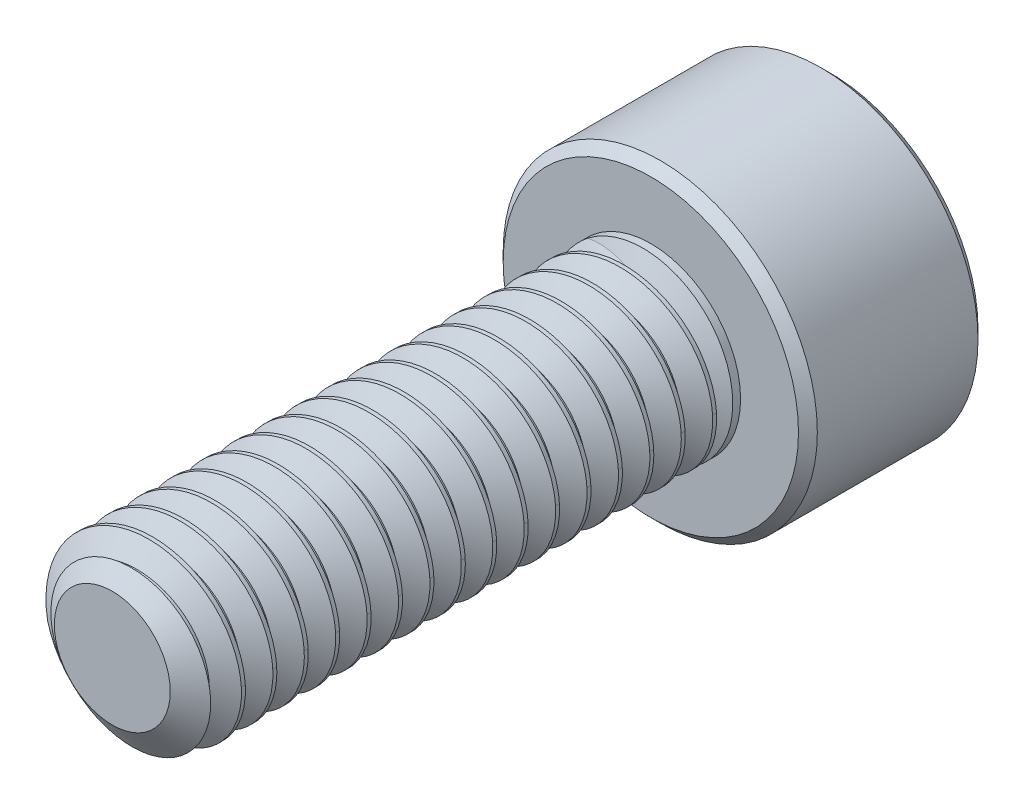
SolidWorks part; units mm, degrees
ref_plane "Front Plane" through (0, 0, 0) normal (0, 0, 1) x (1, 0, 0)
ref_plane "Top Plane" through (0, 0, 0) normal (0, 1, 0) x (1, 0, 0)
ref_plane "Right Plane" through (0, 0, 0) normal (1, 0, 0) x (0, 0, -1)
sketch "Sketch1" plane through (0, 0, 0) normal (0, 0, 1) x (1, 0, 0)
  circle A0 centre (0, 0) radius 2
  dimension "OD" = 4
extrude "Extrude1" add sketch "Sketch1" against normal blind 12
sketch "Sketch2" plane through (0, 0, 0) normal (0, 0, 1) x (1, 0, 0)
  circle A0 centre (0, 0) radius 2 construction
  circle A1 centre (0, 0) radius 2
curve "Helix/Spiral1" pitch 0.7 height 12.7 radius 2 centre (0, 0, 0) axis (0, 0, -1) start towards (0, 1, 0) parameters "pitch"=0.7
sketch "Sketch3" plane through (0, 0, 0) normal (1, 0, 0) x (0, 0, -1)
  line L0 (-0.6125, 2) -> (-0.35, 1.5453)
  line L1 (-0.35, 1.5453) -> (-0.2625, 1.5453)
  line L2 (-0.2625, 1.5453) -> (0, 2)
  line L3 (-0.6125, 2) -> (0, 2)
  line L4 (-0.3063, 2) -> (-0.3063, 1.5453) construction
  line L5 (-0.4813, 1.7727) -> (-0.1313, 1.7727) construction
  line L6 (0, 2) -> (0, -2) construction
  line L7 (0, -2) -> (12, -2) construction
  point P11 (3.15, -2)
  dimension "D1" = 0.0875
  dimension "D2" = 0.35
  dimension "D3" = 60
  dimension "D4" = 3.15
sweep "Cut-Sweep1" cut profiles "Sketch3" path "Helix/Spiral1" align with end faces yes
sketch "Sketch4" plane through (0, 0, 0) normal (1, 0, 0) x (0, 0, -1)
  line L0 (0.4962, 2) -> (0, 1.2913)
  line L1 (0, 1.2913) -> (0, 2)
  line L2 (0.4962, 2) -> (0, 2)
  line L3 (-0.6125, 2) -> (0, 2) construction
  line L4 (0, 0) -> (7.0209, 0) construction
  dimension "D1" = 55
  dimension "D2" = 0.254
revolve "Cut-Revolve1" cut sketch "Sketch4" angle 360 about L4
sketch "Sketch5" plane through (0, 0, 0) normal (1, 0, 0) x (0, 0, -1)
  line L0 (12, -0.9741) -> (12, 1.9864) construction
  line L1 (12, 2) -> (0.1203, 2)
  line L2 (12, 2) -> (12, 0)
  line L3 (12, 0) -> (0.0001, 0)
  line L4 (0.0001, 1.6698) -> (0.0001, 0)
  line L5 (0.1203, 2) -> (0.0001, 1.6698)
  line L6 (0, 0) -> (9.9695, 0) construction
  point P3 (0.0001, 2)
  point P10 (0.0001, 2)
  dimension "D1" = 0.3302
  dimension "Thread min" = 0.0001
  dimension "D3" = 20
revolve "partially thread" [suppressed] add sketch "Sketch5" angle 360 about L6
sketch "Sketch6" plane through (0, 0, -12) normal (0, 0, -1) x (-1, 0, 0)
  circle A0 centre (0, 0) radius 3.5
  dimension "head dia" = 7
extrude "Extrude2" add sketch "Sketch6" along normal blind 4
sketch "Sketch7" plane through (0, 0, -16) normal (0, 0, -1) x (-1, 0, 0)
  line L1 (0, 1.7321) -> (-1.5, 0.866)
  line L2 (-1.5, 0.866) -> (-1.5, -0.866)
  line L3 (-1.5, -0.866) -> (0, -1.7321)
  line L4 (0, -1.7321) -> (1.5, -0.866)
  line L5 (1.5, -0.866) -> (1.5, 0.866)
  line L6 (1.5, 0.866) -> (0, 1.7321)
  circle A0 centre (0, 0) radius 1.5 construction
  dimension "hex dia" = 3
extrude "Cut-Extrude1" cut sketch "Sketch7" against normal blind 2.25
sketch "Sketch8" plane through (0, 0, -16) normal (0, 0, -1) x (-1, 0, 0)
  circle A0 centre (0, 0) radius 1.7321
extrude "Cut-Extrude2" cut sketch "Sketch8" against normal through all draft 45
chamfer "Chamfer1" distance 0.21 angle 45 2 edges at (-3.5, 0, -16) (-3.5, 0, -12)
sketch "Sketch9" plane through (0, 0, 0) normal (1, 0, 0) x (0, 0, -1)
  line L0 (0, 2) -> (0, -2) construction
  line L1 (3.85, 2) -> (3.85, -2) construction
  dimension "D1" = 3.85
sketch "Sketch10" plane through (0, 0, 0) normal (1, 0, 0) x (0, 0, -1)
  line L0 (12, 2) -> (12, 0)
  line L1 (12, 2) -> (11.825, 2)
  line L2 (11.825, 2) -> (10.9966, 0)
  line L3 (12, 0) -> (10.9966, 0)
  line L4 (12, 3.29) -> (12, -3.29) construction
  dimension "D1" = 22.5
  dimension "D2" = 0.175
revolve "Revolve1" add sketch "Sketch10" angle 360 about L3
equation "\"D3@Helix/Spiral1\" = \"screw length@Extrude1\"+\"pitch@Helix/Spiral1\""
equation "\"D1@Sketch3\" = \"pitch@Helix/Spiral1\"*.125"
equation "\"D2@Sketch3\" = \"pitch@Helix/Spiral1\"*.5"
equation "\"D1@Cut-Extrude1\" = \"hex dia@Sketch7\"*.75"
equation "\"D1@Chamfer1\" = \"head dia@Sketch6\"*.03"
equation "\"D1@Sketch9\" = \"pitch@Helix/Spiral1\"*5.5"
equation "\"D2@Sketch10\" = \"pitch@Helix/Spiral1\"*.25"
equation "\"D4@Sketch3\" = \"pitch@Helix/Spiral1\"*4.50"
